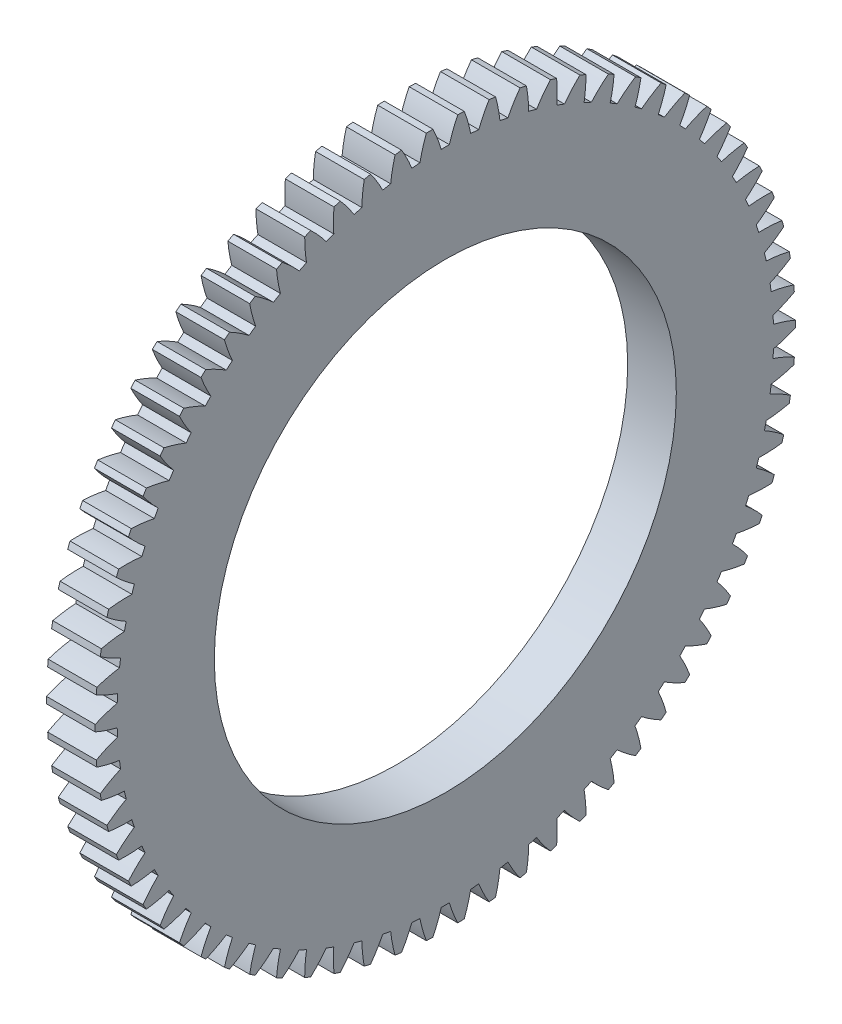
SolidWorks part; units mm, degrees
ref_plane "Plane1" through (0, 0, 0) normal (0, 0, 1) x (1, 0, 0)
ref_plane "Plane2" through (0, 0, 0) normal (0, 1, 0) x (1, 0, 0)
ref_plane "Plane3" through (0, 0, 0) normal (1, 0, 0) x (0, 0, -1)
other "Configuration Table"
sketch "HoldingSke" plane through (0, 0, 0) normal (0, 1, 0) x (1, 0, 0)
  line L0 (0, 0) -> (0.171, -0.4698)
  line L1 (-15, 0) -> (100, 0) construction
  line L2 (0, 0) -> (-2.1039, 2.3779)
  line L3 (0, 0) -> (-11.863, 4.5341)
  line L4 (0, 0) -> (2.9537, 8.1152)
  line L5 (0, 0) -> (-46.8476, -17.4728)
  line L6 (0, 0) -> (-8.2896, -5.593)
  line L7 (-2.1039, 2.3779) -> (8.6586, 51.2059)
  line L8 (-76.2, 54.61) -> (-69.8, 54.61)
  line L9 (-71.009, 38.7566) -> (-53.1078, 45.2721)
  line L10 (-76.2, 71.12) -> (104.1128, 71.12)
  line L11 (0, 0) -> (-10, 0)
  line L12 (-76.2, 101.6) -> (-76.133, 101.6)
  line L13 (24.9733, 27.94) -> (52.9518, 28.4284)
  line L14 (24.9733, 27.94) -> (24.9743, 27.94)
  line L15 (24.9733, 27.94) -> (100.4006, 29.5858)
  line L16 (-63.627, -2) -> (-12.827, -2)
  circle A0 centre (0, 0) radius 47.5
  circle A1 centre (0, 0) radius 37.5
  circle A2 centre (0, 0) radius 37.5
  circle A3 centre (0, 0) radius 47.5
  dimension "Num_teeth" = 70
  dimension "Pitch_radius" = 180.3128
  dimension "Width" = 10
  dimension "Thickness" = 10
sketch "BasProSke" plane through (0, 0, 0) normal (0, 1, 0) x (1, 0, 0)
  line L0 (-10, 0) -> (60, 0) construction
  line L1 (0, 0) -> (0, 72)
  line L2 (0, 0) -> (10, 0)
  line L3 (10, 0) -> (10, 72)
  line L4 (10, 72) -> (0, 72)
  dimension "Thickness" = 10
  dimension "Diameter" = 144
revolve "Base-Revolve" add sketch "BasProSke" angle 360 about L0
sketch "TooCutSke" plane through (0, 0, 0) normal (1, 0, 0) x (0, 0, -1)
  line L1 (0, 0) -> (0, 107) construction
  line L2 (0, 0) -> (-1.6879, 69.9796) construction
  line L3 (0, 0) -> (-6.2797, 139.8289) construction
  line L4 (-1.6879, 69.9796) -> (-3.1399, 69.9144) construction
  arc A0 (0.8345, 67.4938) -> (-0.8345, 67.4938) centre (0, 0) ccw
  arc A1 (2.5731, 71.9794) -> (-2.5731, 71.9794) centre (0, 0) ccw
  circle A2 centre (0, 0) radius 70 construction
  circle A3 centre (0, 0) radius 65.7785 construction
  arc A4 (-0.8345, 67.4938) -> (-2.5731, 71.9794) centre (-27.7148, 59.6548) ccw
  arc A5 (2.5731, 71.9794) -> (0.8345, 67.4938) centre (27.7148, 59.6548) ccw
extrude "ToothCut" cut sketch "TooCutSke" along normal through all
fillet "Breaks" [suppressed] radius 0.04 tangent propagation no
fillet "RootFillets" [suppressed] radius 0.501
pattern_circular "TeethCuts" count 70 every 5.143 about axis through (-10, 0, 0) along (1, 0, 0) of "ToothCut", "RootFillets", "Breaks"
sketch "HubNeaOneSke" plane through (0, 0, 0) normal (-1, 0, 0) x (0, 0, 1)
  circle A0 centre (0, 0) radius 37.5
  dimension "Diameter" = 75
extrude "HubNearOne" [suppressed] add sketch "HubNeaOneSke" along normal blind 40.0001
sketch "HubNeaBotSke" plane through (0, 0, 0) normal (-1, 0, 0) x (0, 0, 1)
  circle A0 centre (0, 0) radius 37.5
  dimension "Diameter" = 75
extrude "HubNearBoth" [suppressed] add sketch "HubNeaBotSke" along normal blind 20
ref_plane "FarPln" through (10, 0, 0) normal (1, 0, 0) x (0, 0, -1)
sketch "HubFarSke" plane through (10, 0, 0) normal (1, 0, 0) x (0, 0, -1)
  circle A0 centre (0, 0) radius 37.5
  dimension "Diameter" = 75
extrude "HubFar" [suppressed] add sketch "HubFarSke" along normal blind 20
sketch "BorSke" plane through (0, 0, 0) normal (1, 0, 0) x (0, 0, -1)
  circle A0 centre (0, 0) radius 47.5
  dimension "Diameter" = 95
extrude "Bore" cut sketch "BorSke" along normal mid plane 100.0001
sketch "KeySke" plane through (0, 0, 0) normal (1, 0, 0) x (0, 0, -1)
  line L0 (-14, 0) -> (-14, 53.9)
  line L1 (-14, 53.9) -> (14, 53.9)
  line L2 (14, 53.9) -> (14, 0)
  line L3 (0, 0) -> (0, 34) construction
  line L4 (-14, 0) -> (14, 0)
  dimension "Width" = 28
extrude "Keyway" [suppressed] cut sketch "KeySke" along normal mid plane 100.0001
pattern_circular "Keyway2" [suppressed] count 2 every 90 about axis through (-10, 0, 0) along (1, 0, 0) reverse direction yes
equation "' \"Module@HoldingSke\" = 6.35"
equation "' \"Num_teeth@HoldingSke\" = 12"
equation "' \"Ap@HoldingSke\" =  20"
equation "' \"Ap@HoldingSke\" = 20"
equation "' \"Width@HoldingSke\" = 0.5 * 25.4"
equation "' \"Hub_dia@HoldingSke\"= 1 * 25.4"
equation "' \"Hub_dia@HoldingSke\" = 1 * 25.4"
equation "' \"Overall_len@HoldingSke\" = 1.0 * 25.4"
equation "' \"Bore@HoldingSke\" = 0.75 * 25.4"
equation "' \"T_dim@HoldingSke\" = 0.1 * 25.4"
equation "' \"Width@KeySke\" = 0.25 * 25.4"
equation "' \"Show_teeth@HoldingSke\" = 13"
equation "' \"Backlash@HoldingSke\" = 0.009 * 25.4"
equation "' \"Addendum_fac@HoldingSke\" = 1.0"
equation "' \"Dedendum_fac@HoldingSke\" = 1.25"
equation "' \"Dedendum_add@HoldingSke\" = 0.00005 * 25.4"
equation "' \"Clearance_fac@HoldingSke\" = 0.25"
equation "\"Pitch@HoldingSke\" = 1 / \"Module@HoldingSke\""
equation "\"Overcut_dia@TooCutSke\" = (\"Num_teeth@HoldingSke\" + 2 * \"Addendum_fac@HoldingSke\") / \"Pitch@HoldingSke\" + 0.002 * 25.4"
equation "\"Pitch_dia@TooCutSke\" = \"Num_teeth@HoldingSke\" / \"Pitch@HoldingSke\""
equation "\"Base_dia@TooCutSke\" = \"Num_teeth@HoldingSke\" / \"Pitch@HoldingSke\" * cos((\"Ap@HoldingSke\"  * 3.14159265 / 180))"
equation "\"Root_dia@TooCutSke\" = (\"Num_teeth@HoldingSke\" + 2) / \"Pitch@HoldingSke\" - 2 * (\"Addendum_fac@HoldingSke\" + \"Dedendum_fac@HoldingSke\") / \"Pitch@HoldingSke\" - \"Dedendum_add@HoldingSke\" * 2"
equation "\"Half_ang@TooCutSke\" = 180 / \"Num_teeth@HoldingSke\""
equation "\"Half_CT@TooCutSke\" = \"Num_teeth@HoldingSke\" / \"Pitch@HoldingSke\" * sin((3.14159265 / 2 / \"Num_teeth@HoldingSke\")) / 2 - 7 * \"Backlash@HoldingSke\" / 4"
equation "\"Flank_rad@TooCutSke\" = \"Num_teeth@HoldingSke\" / \"Pitch@HoldingSke\" / 5"
equation "\"Radius@RootFillets\" = \"Clearance_fac@HoldingSke\" / \"Pitch@HoldingSke\" + \"Dedendum_add@HoldingSke\""
equation "\"Break_rad@Breaks\" = 0.02 / \"Pitch@HoldingSke\""
equation "\"Thickness@HoldingSke\" = \"Width@HoldingSke\""
equation "\"OAL@HoldingSke\" = \"Thickness@HoldingSke\""
equation "\"MHD@HoldingSke\" = (\"Num_teeth@HoldingSke\" + 2) / \"Pitch@HoldingSke\" - 2 * (\"Addendum_fac@HoldingSke\" + \"Dedendum_fac@HoldingSke\")  / \"Pitch@HoldingSke\" - \"Dedendum_add@HoldingSke\" * 2"
equation "\"MBD@HoldingSke\" = (\"Num_teeth@HoldingSke\" + 2) / \"Pitch@HoldingSke\" - 2 * (\"Addendum_fac@HoldingSke\" + \"Dedendum_fac@HoldingSke\")  / \"Pitch@HoldingSke\" - \"Dedendum_add@HoldingSke\" * 2 - 0.002 * 25.4"
equation "\"MHD@HoldingSke\" = ((sgn( \"MHD@HoldingSke\" - \"Hub_dia@HoldingSke\" )-1)*( \"MHD@HoldingSke\" - \"Hub_dia@HoldingSke\" ))/-2+ \"Hub_dia@HoldingSke\""
equation "\"MBD@HoldingSke\" = ((sgn( \"MBD@HoldingSke\" - \"Bore@HoldingSke\" )-1)*( \"MBD@HoldingSke\" - \"Bore@HoldingSke\" ))/-2+ \"Bore@HoldingSke\""
equation "\"OAL@HoldingSke\" = ((sgn( \"OAL@HoldingSke\" - \"Overall_len@HoldingSke\" )+1)*( \"OAL@HoldingSke\" - \"Overall_len@HoldingSke\" ))/2 + \"Overall_len@HoldingSke\" + 0.000002 * 25.4"
equation "\"Num_teeth@TeethCuts\" = int( \"Show_teeth@HoldingSke\" ) + 1"
equation "\"Num_teeth@TeethCuts\" = ((sgn( \"Num_teeth@TeethCuts\" - \"Num_teeth@HoldingSke\" )-1)*( \"Num_teeth@TeethCuts\" - \"Num_teeth@HoldingSke\" ))/-2+ \"Num_teeth@HoldingSke\""
equation "\"Num_teeth@TeethCuts\" = ((sgn( \"Num_teeth@TeethCuts\" - 2.0)+1)*( \"Num_teeth@TeethCuts\" - 2.0))/2 +2.0"
equation "\"Angle@TeethCuts\" = 360.0 / \"Num_teeth@HoldingSke\""
equation "\"Diameter@BasProSke\" = (\"Num_teeth@HoldingSke\" + 2 * \"Addendum_fac@HoldingSke\") / \"Pitch@HoldingSke\""
equation "\"Thickness@BasProSke\"  = \"Thickness@HoldingSke\""
equation "' \"Fillet_rad@BasProSke\" =  \"Thickness@HoldingSke\" * 0.05"
equation "' \"Fillet_rad@BasProSke\" = \"Thickness@HoldingSke\" * 0.05"
equation "\"MHD@HoldingSke\" = ((sgn( \"MHD@HoldingSke\" - \"Root_dia@TooCutSke\" )-1)*( \"MHD@HoldingSke\" - \"Root_dia@TooCutSke\" ))/-2+ \"Root_dia@TooCutSke\""
equation "\"Diameter@HubNeaOneSke\" = \"MHD@HoldingSke\""
equation "\"Length@HubNearOne\" = \"OAL@HoldingSke\" - \"Thickness@BasProSke\""
equation "\"Diameter@HubNeaBotSke\" = \"MHD@HoldingSke\""
equation "\"Length@HubNearBoth\" = ( \"OAL@HoldingSke\" - \"Thickness@BasProSke\" ) / 2.0"
equation "\"Thickness@FarPln\" = \"Thickness@BasProSke\""
equation "\"Diameter@HubFarSke\" = \"MHD@HoldingSke\""
equation "\"Length@HubFar\" = ( \"OAL@HoldingSke\" - \"Thickness@BasProSke\" ) / 2.0"
equation "\"Diameter@BorSke\" = \"MBD@HoldingSke\""
equation "\"D1@Bore\" = \"OAL@HoldingSke\" * 2.0"
equation "\"D1@Keyway\" = \"OAL@HoldingSke\" * 2.0"
equation "\"Offset@KeySke\" = \"T_dim@HoldingSke\" + \"MBD@HoldingSke\" / 2.0"
